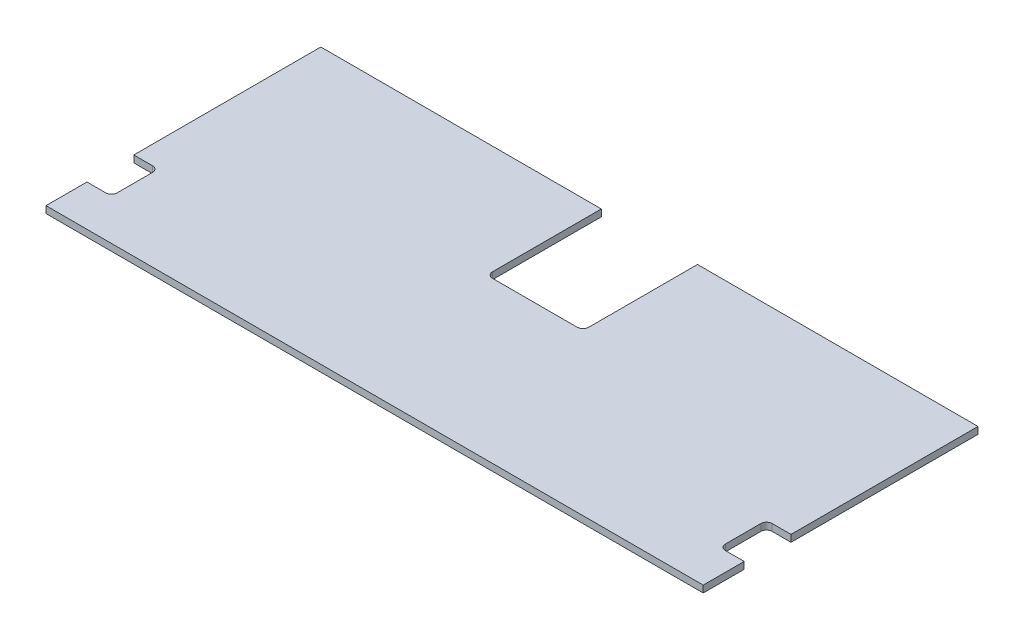
SolidWorks part; units mm, degrees
material "Acrílico (Impacto medio-alto)"
ref_plane "Alzado" through (0, 0, 0) normal (0, 0, 1) x (1, 0, 0)
ref_plane "Planta" through (0, 0, 0) normal (0, 1, 0) x (1, 0, 0)
ref_plane "Vista lateral" through (0, 0, 0) normal (1, 0, 0) x (0, 0, -1)
sketch "Sketch1" plane through (0, 0, 0) normal (0, 1, 0) x (1, 0, 0)
  line L1 (-143.5, -60) -> (143.5, -60)
  line L2 (-143.5, -60) -> (-143.5, 60)
  line L3 (-143.5, 60) -> (143.5, 60)
  line L4 (143.5, -60) -> (143.5, 60)
  line L5 (-143.5, -60) -> (143.5, 60) construction
  line L6 (-143.5, 60) -> (143.5, -60) construction
  point P0 (0, 0)
  dimension "D1" = 120
  dimension "D2" = 287
extrude "Boss-Extrude1" add sketch "Sketch1" along normal blind 3
sketch "Sketch2" plane through (0, 3, 0) normal (0, 1, 0) x (1, 0, 0)
  line L0 (0, 0) -> (0, 31) construction
  line L1 (-21, 10) -> (21, 10)
  line L2 (-21, 10) -> (-21, 52)
  line L3 (-21, 52) -> (21, 52) construction
  line L4 (21, 10) -> (21, 52)
  line L5 (-21, 10) -> (21, 52) construction
  line L6 (-21, 52) -> (21, 10) construction
  line L7 (143.5, 60) -> (-143.5, 60) construction
  line L8 (-21, 52) -> (-21, 60)
  line L9 (-21, 60) -> (21, 60)
  line L10 (21, 60) -> (21, 52)
  line L11 (143.5, -60) -> (143.5, 60) construction
  line L12 (143.5, -21.6575) -> (132.8028, -21.6575)
  line L13 (143.5, -21.6575) -> (143.5, -42.1119)
  line L14 (143.5, -42.1119) -> (132.8028, -42.1119)
  line L15 (132.8028, -21.6575) -> (132.8028, -42.1119)
  line L16 (0, -940) -> (0, 49060) construction
  line L17 (-143.5, -42.1119) -> (-132.8028, -42.1119)
  line L18 (-143.5, -21.6575) -> (-132.8028, -21.6575)
  line L19 (-132.8028, -21.6575) -> (-132.8028, -42.1119)
  line L20 (-143.5, -21.6575) -> (-143.5, -42.1119)
  point P0 (0, 31)
  point P21 (0, 60)
  dimension "D1" = 42
  dimension "D2" = 42
  dimension "D3" = 8
extrude "Cut-Extrude1" cut sketch "Sketch2" against normal through all
fillet "Fillet1" radius 2.5 6 edges at (-21, 1.5, -10) (21, 1.5, -10) (132.8028, 1.5, 42.1119) (132.8028, 1.5, 21.6575) (-132.8028, 1.5, 42.1119) (-132.8028, 1.5, 21.6575)
